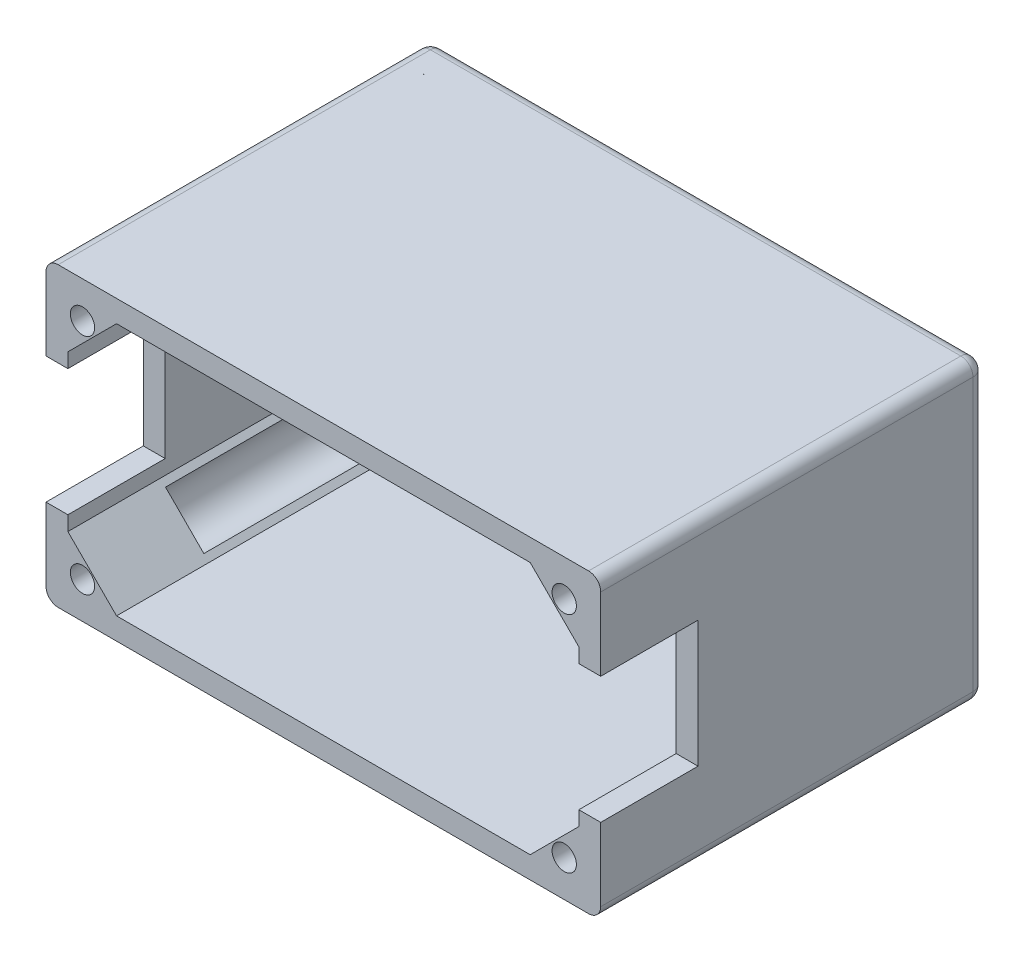
SolidWorks part; units mm, degrees
ref_plane "前视基准面" through (0, 0, 0) normal (0, 0, 1) x (1, 0, 0)
ref_plane "上视基准面" through (0, 0, 0) normal (0, 1, 0) x (1, 0, 0)
ref_plane "右视基准面" through (0, 0, 0) normal (1, 0, 0) x (0, 0, -1)
sketch "草图1" plane through (0, 0, 0) normal (0, 0, 1) x (1, 0, 0)
  line L1 (-11.4, 6.1) -> (11.4, 6.1)
  line L2 (-11.4, 6.1) -> (-11.4, -6.1)
  line L3 (-11.4, -6.1) -> (11.4, -6.1)
  line L4 (11.4, 6.1) -> (11.4, -6.1)
  line L5 (-11.4, 6.1) -> (11.4, -6.1) construction
  line L6 (-11.4, -6.1) -> (11.4, 6.1) construction
  point P0 (0, 0)
  dimension "D1" = 22.8
  dimension "D2" = 12.2
extrude "凸台-拉伸1" add sketch "草图1" along normal blind 15.8
sketch "草图2" plane through (0, 0, 15.8) normal (0, 0, 1) x (1, 0, 0)
  line L0 (11.4, 6.1) -> (-11.4, 6.1) construction
  line L1 (-10.5, 5.2) -> (10.5, 5.2)
  line L2 (-10.5, 5.2) -> (-10.5, -5.2)
  line L3 (-10.5, -5.2) -> (10.5, -5.2)
  line L4 (10.5, 5.2) -> (10.5, -5.2)
  line L5 (-11.4, 6.1) -> (-11.4, -6.1) construction
  line L6 (-11.4, -6.1) -> (11.4, -6.1) construction
  line L7 (11.4, -6.1) -> (11.4, 6.1) construction
  dimension "D1" = 0.9
  dimension "D2" = 0.9
  dimension "D3" = 0.9
  dimension "D4" = 0.9
extrude "切除-拉伸1" cut sketch "草图2" against normal blind 13.8
sketch "草图3" plane through (0, 0, 2) normal (0, 0, 1) x (1, 0, 0)
  line L0 (10.5, -5.2) -> (10.5, 5.2) construction
  line L1 (10.5, 5.2) -> (-10.5, 5.2) construction
  line L2 (10.5, -5.2) -> (10.5, 5.2) construction
  line L3 (-10.5, -5.2) -> (10.5, -5.2) construction
  line L4 (-10.5, 5.2) -> (-10.5, -5.2) construction
  circle A0 centre (9.9, 4.6) radius 0.5
  circle A1 centre (-9.9, -4.6) radius 0.5
  circle A2 centre (9.9, -4.6) radius 0.5
  circle A3 centre (-9.9, 4.6) radius 0.5
  dimension "D1" = 1
  dimension "D5" = 1
  dimension "D7" = 1
  dimension "D10" = 0.6
  dimension "D11" = 1
  dimension "D2" = 0.6
  dimension "D3" = 0.6
  dimension "D4" = 19.8
  dimension "D6" = 0.6
  dimension "D8" = 0.6
  dimension "D9" = 0.6
  dimension "D12" = 0.6
sketch "草图4" plane through (0, 0, 15.8) normal (0, 0, 1) x (1, 0, 0)
  line L0 (-11.4, 6.1) -> (-11.4, -6.1) construction
  line L1 (-11.4, 2.6) -> (-10.5, 2.6)
  line L2 (-11.4, 2.6) -> (-11.4, -2.6)
  line L3 (-11.4, -2.6) -> (-10.5, -2.6)
  line L4 (-10.5, 2.6) -> (-10.5, -2.6)
  line L5 (-10.5, 5.2) -> (-10.5, -5.2) construction
  line L6 (11.4, 6.1) -> (-11.4, 6.1) construction
  line L8 (-11.4, -6.1) -> (11.4, -6.1) construction
  dimension "D1" = 3.5
  dimension "D2" = 3.5
extrude "切除-拉伸2" cut sketch "草图4" against normal blind 4
sketch "草图7" plane through (0, 0, 2) normal (0, 0, 1) x (1, 0, 0)
  line L0 (-5.85, -2.45) -> (5.15, -2.45) construction
  line L1 (-5.85, -0.2) -> (5.15, -0.2)
  line L2 (-5.85, -4.7) -> (5.15, -4.7)
  line L3 (-10.5, -5.2) -> (10.5, -5.2) construction
  line L5 (10.5, -5.2) -> (10.5, 5.2) construction
  arc A0 (-5.85, -0.2) -> (-5.85, -4.7) centre (-5.85, -2.45) ccw
  arc A1 (5.15, -4.7) -> (5.15, -0.2) centre (5.15, -2.45) ccw
  point P2 (-0.35, -2.45)
  point P7 (-8.1, -2.45)
  point P8 (7.4, -2.45)
  dimension "D2" = 15.5
  dimension "D1" = 11
  dimension "D3" = 0.5
  dimension "D4" = 10.85
extrude "切除-拉伸5" cut sketch "草图7" against normal blind 2
fillet "圆角2" radius 0.5 4 edges at (11.4, 6.1, 7.9) (11.4, -6.1, 7.9) (-11.4, -6.1, 7.9) (-11.4, 6.1, 7.9)
sketch "草图8" plane through (0, 0, 15.8) normal (0, 0, 1) x (1, 0, 0)
  line L0 (10.5, -5.2) -> (10.5, 5.2) construction
  line L1 (10.5, 2.6) -> (11.4, 2.6)
  line L2 (10.5, 2.6) -> (10.5, -2.6)
  line L3 (10.5, -2.6) -> (11.4, -2.6)
  line L4 (11.4, 2.6) -> (11.4, -2.6)
  line L5 (11.4, -5.6) -> (11.4, 5.6) construction
  line L6 (10.9, 6.1) -> (-10.9, 6.1) construction
  line L7 (-10.9, -6.1) -> (10.9, -6.1) construction
  dimension "D1" = 3.5
  dimension "D2" = 3.5
extrude "切除-拉伸6" cut sketch "草图8" against normal blind 4
sketch "草图10" plane through (0, 0, 2) normal (0, 0, 1) x (1, 0, 0)
  line L0 (-10.5, -2.6) -> (-10.5, -5.2) construction
  line L1 (-10.5, -5.2) -> (10.5, -5.2) construction
  line L2 (-10.5, 5.2) -> (-10.5, -5.2) construction
  line L3 (-10.5, -5.2) -> (10.5, -5.2) construction
  line L4 (10.5, 5.2) -> (-10.5, 5.2) construction
  line L5 (10.5, -5.2) -> (10.5, 5.2) construction
  line L6 (10.5, -5.2) -> (10.5, -2.6) construction
  line L7 (10.5, 5.2) -> (-10.5, 5.2) construction
  line L8 (-10.5, 5.2) -> (-10.5, 2.6) construction
  line L9 (-10.5, 3.2) -> (-10.5, 5.2)
  line L10 (10.5, 2.6) -> (10.5, 5.2) construction
  line L11 (8.5, 5.2) -> (10.5, 5.2)
  line L12 (10.5, 5.2) -> (10.5, 3.2)
  line L13 (-10.5, 5.2) -> (-8.5, 5.2)
  line L14 (10.5, -3.2) -> (10.5, -5.2)
  line L15 (10.5, -5.2) -> (8.5, -5.2)
  line L16 (-10.5, -3.2) -> (-10.5, -5.2)
  line L17 (-10.5, -5.2) -> (-8.5, -5.2)
  line L18 (8.5, 5.2) -> (10.5, 3.2)
  line L19 (10.5, -3.2) -> (8.5, -5.2)
  line L20 (-10.5, -3.2) -> (-8.5, -5.2)
  line L21 (-8.5, 5.2) -> (-10.5, 3.2)
  dimension "D7" = 2
  dimension "D10" = 2
  dimension "D1" = 2
  dimension "D2" = 2
  dimension "D4" = 2
  dimension "D5" = 2
  dimension "D8" = 2
  dimension "D11" = 2
extrude "凸台-拉伸2" add sketch "草图10" along normal blind 13.8
extrude "切除-拉伸8" cut sketch "草图3" along normal through all and the other way through all
sketch "草图9" plane through (0, 0, 0) normal (0, 0, -1) x (-1, 0, 0)
  circle A0 centre (-9.9, 4.6) radius 1.25
  circle A1 centre (9.9, 4.6) radius 1.25
  circle A3 centre (-9.9, -4.6) radius 1.25
  circle A4 centre (9.9, -4.6) radius 1.25
  dimension "D1" = 2.5
  dimension "D2" = 2.5
  dimension "D3" = 2.5
  dimension "D4" = 2.5
extrude "切除-拉伸9" cut sketch "草图9" against normal blind 12
fillet "圆角3" radius 0.5 8 edges at (-11.2536, 5.9536, 0) (-11.4, 0, 0) (-11.2536, -5.9536, 0) (0, -6.1, 0) (11.2536, -5.9536, 0) (11.2536, 5.9536, 0) (11.4, 0, 0) (0, 6.1, 0)
